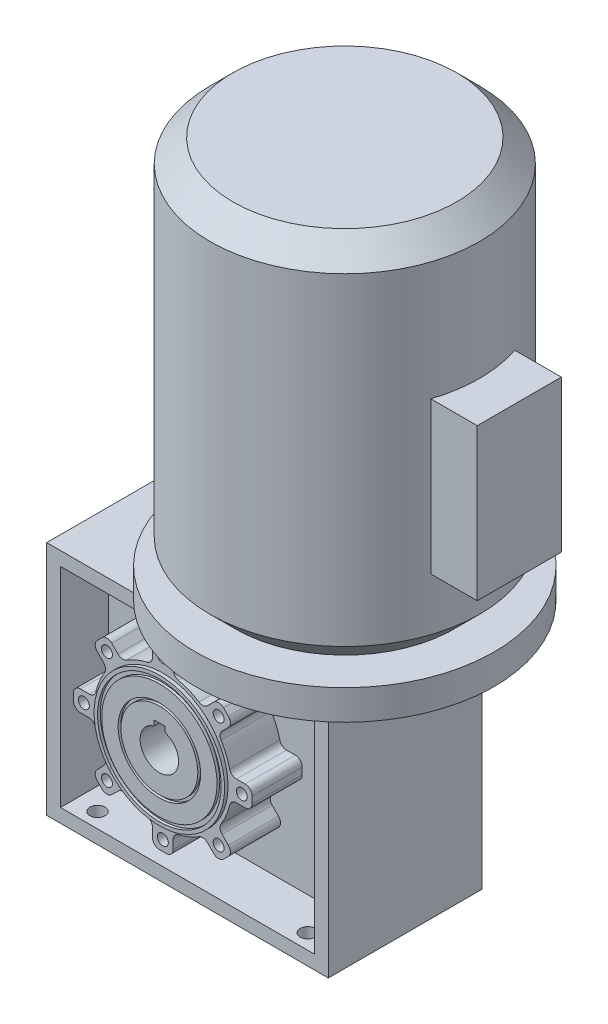
SolidWorks part; units mm, degrees
material "201 Annealed Stainless Steel (SS)"
ref_plane "Front Plane" through (0, 0, 0) normal (0, 0, 1) x (1, 0, 0)
ref_plane "Top Plane" through (0, 0, 0) normal (0, 1, 0) x (1, 0, 0)
ref_plane "Right Plane" through (0, 0, 0) normal (1, 0, 0) x (0, 0, -1)
sketch "Sketch1" plane through (0, 0, 0) normal (0, 0, 1) x (1, 0, 0)
  line L0 (214, -77.2819) -> (214, 49.2287) construction
  line L1 (61, -65.4596) -> (61, 55.7174) construction
  line L2 (125, 99.4164) -> (125, 103.3) construction
  line L3 (125, 103.3) -> (117, 103.3) construction
  line L4 (117, 103.3) -> (117, 99.4164) construction
  line L5 (121, 86) -> (121, 117.4858) construction
  line L8 (35, 0) -> (240, 0)
  line L9 (240, 0) -> (240, 172)
  line L10 (240, 172) -> (35, 172)
  line L11 (35, 172) -> (35, 0)
  circle A1 centre (121, 86) radius 14
  dimension "D1" = 86
  dimension "D2" = 86
  dimension "D6" = 28
  dimension "D3" = 205
  dimension "D4" = 172
  dimension "D5" = 35
  dimension "D7" = 93
  dimension "D8" = 60
  dimension "D9" = 31.3
  dimension "D10" = 8
extrude "Boss-Extrude1" add sketch "Sketch1" against normal blind 112
ref_plane "Plane1" through (0, 0, -56) normal (0, 0, 1) x (1, 0, 0)
sketch "Sketch3" plane through (0, 172, 0) normal (0, 1, 0) x (1, 0, 0)
  circle A1 centre (228, 65) radius 110
sketch "Sketch2" plane through (0, 0, -56) normal (0, 0, 1) x (1, 0, 0)
  line L0 (196, 62.1488) -> (196, 501.4136) construction
  line L1 (275.7058, 209.9069) -> (294.1112, 228.3123)
  line L2 (294.1112, 228.3123) -> (294.1112, 463.3395)
  line L3 (294.1112, 463.3395) -> (277.4507, 480)
  line L4 (277.4507, 480) -> (196, 480)
  line L5 (35, 0) -> (240, 0) construction
  line L6 (275.7058, 209.9069) -> (304.743, 209.9069)
  line L7 (304.743, 209.9069) -> (304.743, 199)
  line L8 (196, 209.9069) -> (275.7058, 209.9069) construction
  line L9 (196, 172) -> (196, 480)
  line L10 (304.743, 199) -> (237.6683, 199) construction
  line L11 (35, 0) -> (240, 0) construction
  line L12 (237.6683, 188.0931) -> (237.6683, 172)
  line L13 (240, 172) -> (35, 172) construction
  line L14 (237.6683, 172) -> (196, 172)
  line L15 (304.743, 199) -> (304.743, 188.0931)
  line L16 (304.743, 188.0931) -> (237.6683, 188.0931)
  dimension "D1" = 480
  dimension "D2" = 281
  dimension "D3" = 199
  dimension "D4" = 75
  dimension "D5" = 113
  dimension "D6" = 45
  dimension "D7" = 45
revolve "Motor" add sketch "Sketch2" angle 360 about L0
sketch "Sketch4" plane through (0, 0, 0) normal (0, 0, 1) x (1, 0, 0)
  line L8 (230, 10) -> (230, 162)
  line L9 (45, 10) -> (230, 10)
  line L10 (45, 162) -> (45, 10)
  line L11 (230, 162) -> (45, 162)
  line L12 (230, 10) -> (230, 162)
  line L13 (45, 10) -> (230, 10)
  line L14 (45, 162) -> (45, 10)
  line L15 (230, 162) -> (45, 162)
  circle A0 centre (121, 86) radius 50
  circle A1 centre (121, 86) radius 14 construction
  dimension "D2" = 100
  dimension "D1" = 10
extrude "Cut-Extrude1" cut sketch "Sketch4" against normal blind 35
sketch "Sketch5" plane through (0, 0, -112) normal (0, 0, -1) x (-1, 0, 0)
  line L4 (-230, 162) -> (-230, 10)
  line L5 (-45, 162) -> (-230, 162)
  line L6 (-45, 10) -> (-45, 162)
  line L7 (-230, 10) -> (-45, 10)
  line L8 (-230, 162) -> (-230, 10)
  line L9 (-45, 162) -> (-230, 162)
  line L10 (-45, 10) -> (-45, 162)
  line L11 (-230, 10) -> (-45, 10)
  circle A1 centre (-121, 86) radius 50
  circle A2 centre (-121, 86) radius 50
  dimension "D1" = 0
  dimension "D2" = 0
extrude "Cut-Extrude2" cut sketch "Sketch5" against normal blind 46
sketch "Sketch6" plane through (0, 0, 0) normal (0, 0, 1) x (1, 0, 0)
  line L0 (121, 86) -> (121, 219.6781) construction
  line L1 (121, 86) -> (299.9938, 86) construction
  line L2 (113.5, 135.4343) -> (113.5, 151)
  line L3 (113.5, 151) -> (128.5, 151)
  line L4 (128.5, 135.4343) -> (128.5, 151)
  circle A0 centre (121, 143.5) radius 4 construction
  circle A1 centre (121, 28.5) radius 4 construction
  arc A2 (128.5, 135.4343) -> (113.5, 135.4343) centre (121, 86) ccw
  circle A3 centre (121, 86) radius 50 construction
  circle A4 centre (121, 86) radius 57.5 construction
  point P14 (121, 151)
  dimension "D1" = 8
  dimension "D2" = 115
  dimension "D4" = 15
  dimension "D3" = 15
extrude "Boss-Extrude2" add sketch "Sketch6" against normal up to surface (112 mm away) up to face at (135, 86, -112)
ref_axis "Axis1" through (121, 86, -112) along (0, 0, 1)
sketch "Sketch7" plane through (0, 0, 0) normal (0, 0, 1) x (1, 0, 0)
  circle A0 centre (121, 143.5) radius 4 construction
  circle A1 centre (121, 143.5) radius 4
extrude "Cut-Extrude3" cut sketch "Sketch7" against normal through all
fillet "Fillet1" radius 5 8 edges at (128.5, 151, -17.5) (128.5, 135.4343, -17.5) (113.5, 135.4343, -17.5) (113.5, 151, -17.5) (128.5, 135.4343, -89) (128.5, 151, -89) (113.5, 151, -89) (113.5, 135.4343, -89)
pattern_circular "CirPattern1" count 8 over 360 about axis through (121, 86, -112) along (0, 0, 1) of "Boss-Extrude2", "Cut-Extrude3", "Fillet1"
sketch "Sketch8" plane through (0, 0, 0) normal (0, 0, 1) x (1, 0, 0)
  line L4 (88.4302, 129.1764) -> (83.8769, 133.7297)
  line L6 (88.4302, 129.1764) -> (83.8769, 133.7297)
  line L8 (76.8058, 133.7297) -> (73.2703, 130.1942)
  line L10 (76.8058, 133.7297) -> (73.2703, 130.1942)
  line L32 (73.2703, 123.1231) -> (77.8236, 118.5698)
  line L33 (73.2703, 123.1231) -> (77.8236, 118.5698)
  line L34 (67.4393, 93.5) -> (61, 93.5)
  line L35 (67.4393, 93.5) -> (61, 93.5)
  line L36 (56, 88.5) -> (56, 83.5)
  line L37 (56, 88.5) -> (56, 83.5)
  line L38 (61, 78.5) -> (67.4393, 78.5)
  line L39 (61, 78.5) -> (67.4393, 78.5)
  line L40 (77.8236, 53.4302) -> (73.2703, 48.8769)
  line L41 (77.8236, 53.4302) -> (73.2703, 48.8769)
  line L42 (73.2703, 41.8058) -> (76.8058, 38.2703)
  line L43 (73.2703, 41.8058) -> (76.8058, 38.2703)
  line L44 (83.8769, 38.2703) -> (88.4302, 42.8236)
  line L45 (83.8769, 38.2703) -> (88.4302, 42.8236)
  line L46 (113.5, 32.4393) -> (113.5, 26)
  line L47 (113.5, 32.4393) -> (113.5, 26)
  line L72 (118.5, 21) -> (123.5, 21)
  line L73 (118.5, 21) -> (123.5, 21)
  line L74 (128.5, 26) -> (128.5, 32.4393)
  line L75 (128.5, 26) -> (128.5, 32.4393)
  line L76 (153.5698, 42.8236) -> (158.1231, 38.2703)
  line L77 (153.5698, 42.8236) -> (158.1231, 38.2703)
  line L78 (165.1942, 38.2703) -> (168.7297, 41.8058)
  line L79 (165.1942, 38.2703) -> (168.7297, 41.8058)
  line L80 (168.7297, 48.8769) -> (164.1764, 53.4302)
  line L81 (168.7297, 48.8769) -> (164.1764, 53.4302)
  line L82 (174.5607, 78.5) -> (181, 78.5)
  line L83 (174.5607, 78.5) -> (181, 78.5)
  line L84 (186, 83.5) -> (186, 88.5)
  line L85 (186, 83.5) -> (186, 88.5)
  line L86 (181, 93.5) -> (174.5607, 93.5)
  line L87 (181, 93.5) -> (174.5607, 93.5)
  line L88 (164.1764, 118.5698) -> (168.7297, 123.1231)
  line L89 (164.1764, 118.5698) -> (168.7297, 123.1231)
  line L90 (168.7297, 130.1942) -> (165.1942, 133.7297)
  line L91 (168.7297, 130.1942) -> (165.1942, 133.7297)
  line L92 (158.1231, 133.7297) -> (153.5698, 129.1764)
  line L93 (158.1231, 133.7297) -> (153.5698, 129.1764)
  line L94 (128.5, 139.5607) -> (128.5, 146)
  line L95 (128.5, 139.5607) -> (128.5, 146)
  line L96 (123.5, 151) -> (118.5, 151)
  line L97 (123.5, 151) -> (118.5, 151)
  line L98 (113.5, 146) -> (113.5, 139.5607)
  line L99 (113.5, 146) -> (113.5, 139.5607)
  circle A0 centre (161.6586, 45.3414) radius 4 construction
  circle A1 centre (121, 28.5) radius 4 construction
  circle A2 centre (80.3414, 45.3414) radius 4 construction
  circle A3 centre (63.5, 86) radius 4 construction
  circle A4 centre (178.5, 86) radius 4 construction
  circle A5 centre (161.6586, 126.6586) radius 4 construction
  circle A6 centre (121, 86) radius 14 construction
  circle A7 centre (80.3414, 126.6586) radius 4 construction
  circle A24 centre (121, 143.5) radius 4 construction
  circle A25 centre (161.6586, 45.3414) radius 4
  circle A26 centre (121, 28.5) radius 4
  circle A27 centre (80.3414, 45.3414) radius 4
  circle A28 centre (63.5, 86) radius 4
  circle A29 centre (178.5, 86) radius 4
  circle A30 centre (161.6586, 126.6586) radius 4
  circle A31 centre (121, 86) radius 14
  circle A32 centre (80.3414, 126.6586) radius 4
  circle A33 centre (121, 143.5) radius 4
  arc A70 (168.7297, 123.1231) -> (168.7297, 130.1942) centre (165.1942, 126.6586) ccw
  arc A71 (168.7297, 123.1231) -> (168.7297, 130.1942) centre (165.1942, 126.6586) ccw
  arc A72 (165.1942, 133.7297) -> (158.1231, 133.7297) centre (161.6586, 130.1942) ccw
  arc A73 (165.1942, 133.7297) -> (158.1231, 133.7297) centre (161.6586, 130.1942) ccw
  arc A74 (147.3948, 128.4654) -> (153.5698, 129.1764) centre (150.0343, 132.712) ccw
  arc A76 (147.3948, 128.4654) -> (153.5698, 129.1764) centre (150.0343, 132.712) ccw
  arc A78 (147.3948, 128.4654) -> (132.3636, 134.6916) centre (121, 86) ccw
  arc A80 (147.3948, 128.4654) -> (132.3636, 134.6916) centre (121, 86) ccw
  arc A82 (128.5, 139.5607) -> (132.3636, 134.6916) centre (133.5, 139.5607) ccw
  arc A84 (128.5, 139.5607) -> (132.3636, 134.6916) centre (133.5, 139.5607) ccw
  arc A86 (128.5, 146) -> (123.5, 151) centre (123.5, 146) ccw
  arc A88 (128.5, 146) -> (123.5, 151) centre (123.5, 146) ccw
  arc A90 (118.5, 151) -> (113.5, 146) centre (118.5, 146) ccw
  arc A92 (118.5, 151) -> (113.5, 146) centre (118.5, 146) ccw
  arc A94 (109.6364, 134.6916) -> (113.5, 139.5607) centre (108.5, 139.5607) ccw
  arc A96 (109.6364, 134.6916) -> (113.5, 139.5607) centre (108.5, 139.5607) ccw
  arc A98 (109.6364, 134.6916) -> (94.6052, 128.4654) centre (121, 86) ccw
  arc A100 (109.6364, 134.6916) -> (94.6052, 128.4654) centre (121, 86) ccw
  arc A102 (88.4302, 129.1764) -> (94.6052, 128.4654) centre (91.9657, 132.712) ccw
  arc A104 (88.4302, 129.1764) -> (94.6052, 128.4654) centre (91.9657, 132.712) ccw
  arc A106 (83.8769, 133.7297) -> (76.8058, 133.7297) centre (80.3414, 130.1942) ccw
  arc A108 (83.8769, 133.7297) -> (76.8058, 133.7297) centre (80.3414, 130.1942) ccw
  arc A110 (73.2703, 130.1942) -> (73.2703, 123.1231) centre (76.8058, 126.6586) ccw
  arc A112 (73.2703, 130.1942) -> (73.2703, 123.1231) centre (76.8058, 126.6586) ccw
  arc A114 (78.5346, 112.3948) -> (77.8236, 118.5698) centre (74.288, 115.0343) ccw
  arc A116 (78.5346, 112.3948) -> (77.8236, 118.5698) centre (74.288, 115.0343) ccw
  arc A118 (78.5346, 112.3948) -> (72.3084, 97.3636) centre (121, 86) ccw
  arc A120 (78.5346, 112.3948) -> (72.3084, 97.3636) centre (121, 86) ccw
  arc A122 (67.4393, 93.5) -> (72.3084, 97.3636) centre (67.4393, 98.5) ccw
  arc A124 (67.4393, 93.5) -> (72.3084, 97.3636) centre (67.4393, 98.5) ccw
  arc A126 (61, 93.5) -> (56, 88.5) centre (61, 88.5) ccw
  arc A128 (61, 93.5) -> (56, 88.5) centre (61, 88.5) ccw
  arc A130 (56, 83.5) -> (61, 78.5) centre (61, 83.5) ccw
  arc A132 (56, 83.5) -> (61, 78.5) centre (61, 83.5) ccw
  arc A134 (72.3084, 74.6364) -> (67.4393, 78.5) centre (67.4393, 73.5) ccw
  arc A136 (72.3084, 74.6364) -> (67.4393, 78.5) centre (67.4393, 73.5) ccw
  arc A138 (72.3084, 74.6364) -> (78.5346, 59.6052) centre (121, 86) ccw
  arc A140 (72.3084, 74.6364) -> (78.5346, 59.6052) centre (121, 86) ccw
  arc A142 (77.8236, 53.4302) -> (78.5346, 59.6052) centre (74.288, 56.9657) ccw
  arc A144 (77.8236, 53.4302) -> (78.5346, 59.6052) centre (74.288, 56.9657) ccw
  arc A146 (73.2703, 48.8769) -> (73.2703, 41.8058) centre (76.8058, 45.3414) ccw
  arc A147 (73.2703, 48.8769) -> (73.2703, 41.8058) centre (76.8058, 45.3414) ccw
  arc A148 (76.8058, 38.2703) -> (83.8769, 38.2703) centre (80.3414, 41.8058) ccw
  arc A149 (76.8058, 38.2703) -> (83.8769, 38.2703) centre (80.3414, 41.8058) ccw
  arc A150 (94.6052, 43.5346) -> (88.4302, 42.8236) centre (91.9657, 39.288) ccw
  arc A151 (94.6052, 43.5346) -> (88.4302, 42.8236) centre (91.9657, 39.288) ccw
  arc A152 (94.6052, 43.5346) -> (109.6364, 37.3084) centre (121, 86) ccw
  arc A153 (94.6052, 43.5346) -> (109.6364, 37.3084) centre (121, 86) ccw
  arc A154 (113.5, 32.4393) -> (109.6364, 37.3084) centre (108.5, 32.4393) ccw
  arc A155 (113.5, 32.4393) -> (109.6364, 37.3084) centre (108.5, 32.4393) ccw
  arc A156 (113.5, 26) -> (118.5, 21) centre (118.5, 26) ccw
  arc A157 (113.5, 26) -> (118.5, 21) centre (118.5, 26) ccw
  arc A158 (123.5, 21) -> (128.5, 26) centre (123.5, 26) ccw
  arc A159 (123.5, 21) -> (128.5, 26) centre (123.5, 26) ccw
  arc A160 (132.3636, 37.3084) -> (128.5, 32.4393) centre (133.5, 32.4393) ccw
  arc A161 (132.3636, 37.3084) -> (128.5, 32.4393) centre (133.5, 32.4393) ccw
  arc A162 (132.3636, 37.3084) -> (147.3948, 43.5346) centre (121, 86) ccw
  arc A163 (132.3636, 37.3084) -> (147.3948, 43.5346) centre (121, 86) ccw
  arc A164 (153.5698, 42.8236) -> (147.3948, 43.5346) centre (150.0343, 39.288) ccw
  arc A165 (153.5698, 42.8236) -> (147.3948, 43.5346) centre (150.0343, 39.288) ccw
  arc A166 (158.1231, 38.2703) -> (165.1942, 38.2703) centre (161.6586, 41.8058) ccw
  arc A167 (158.1231, 38.2703) -> (165.1942, 38.2703) centre (161.6586, 41.8058) ccw
  arc A168 (168.7297, 41.8058) -> (168.7297, 48.8769) centre (165.1942, 45.3414) ccw
  arc A169 (168.7297, 41.8058) -> (168.7297, 48.8769) centre (165.1942, 45.3414) ccw
  arc A170 (163.4654, 59.6052) -> (164.1764, 53.4302) centre (167.712, 56.9657) ccw
  arc A171 (163.4654, 59.6052) -> (164.1764, 53.4302) centre (167.712, 56.9657) ccw
  arc A172 (163.4654, 59.6052) -> (169.6916, 74.6364) centre (121, 86) ccw
  arc A173 (163.4654, 59.6052) -> (169.6916, 74.6364) centre (121, 86) ccw
  arc A174 (174.5607, 78.5) -> (169.6916, 74.6364) centre (174.5607, 73.5) ccw
  arc A175 (174.5607, 78.5) -> (169.6916, 74.6364) centre (174.5607, 73.5) ccw
  arc A176 (181, 78.5) -> (186, 83.5) centre (181, 83.5) ccw
  arc A177 (181, 78.5) -> (186, 83.5) centre (181, 83.5) ccw
  arc A178 (186, 88.5) -> (181, 93.5) centre (181, 88.5) ccw
  arc A179 (186, 88.5) -> (181, 93.5) centre (181, 88.5) ccw
  arc A180 (169.6916, 97.3636) -> (174.5607, 93.5) centre (174.5607, 98.5) ccw
  arc A181 (169.6916, 97.3636) -> (174.5607, 93.5) centre (174.5607, 98.5) ccw
  arc A182 (169.6916, 97.3636) -> (163.4654, 112.3948) centre (121, 86) ccw
  arc A183 (169.6916, 97.3636) -> (163.4654, 112.3948) centre (121, 86) ccw
  arc A184 (164.1764, 118.5698) -> (163.4654, 112.3948) centre (167.712, 115.0343) ccw
  arc A185 (164.1764, 118.5698) -> (163.4654, 112.3948) centre (167.712, 115.0343) ccw
  dimension "D1" = 0
extrude "Boss-Extrude one side" add sketch "Sketch8" along normal blind 1.5
sketch "Sketch9" plane through (0, 0, 1.5) normal (0, 0, 1) x (1, 0, 0)
  circle A0 centre (121, 86) radius 47.5
  circle A2 centre (121, 86) radius 14
  circle A3 centre (121, 86) radius 14 construction
  dimension "D1" = 95
extrude "Boss-Extrude5" add sketch "Sketch9" along normal blind 2.5
sketch "Sketch10" plane through (0, 0, 4) normal (0, 0, 1) x (1, 0, 0)
  circle A0 centre (121, 86) radius 45
  circle A1 centre (121, 86) radius 42
  dimension "D1" = 90
  dimension "D2" = 84
extrude "Cut-Extrude4" cut sketch "Sketch10" against normal blind 2
sketch "Sketch11" plane through (0, 0, 4) normal (0, 0, 1) x (1, 0, 0)
  circle A0 centre (121, 86) radius 30
  circle A1 centre (121, 86) radius 14 construction
  circle A2 centre (121, 86) radius 28
  dimension "D1" = 60
  dimension "D2" = 2
extrude "Cut-Extrude5" cut sketch "Sketch11" against normal up to surface (2 mm away) up to face at (163, 86, 2)
sketch "Sketch12" plane through (240, 0, 0) normal (1, 0, 0) x (0, 0, -1)
  line L0 (56, 158.4) -> (56, -158.4) construction
  line L1 (25.4071, 377.0348) -> (86.5929, 377.0348)
  line L2 (25.4071, 377.0348) -> (25.4071, 266.6375)
  line L3 (25.4071, 266.6375) -> (86.5929, 266.6375)
  line L4 (86.5929, 377.0348) -> (86.5929, 266.6375)
  line L5 (25.4071, 377.0348) -> (86.5929, 266.6375) construction
  line L6 (25.4071, 266.6375) -> (86.5929, 377.0348) construction
  point P0 (56, 321.8362)
extrude "Boss-Extrude6" add sketch "Sketch12" along normal offset from surface (83 mm away) 288 up to face at (35, 86, -56)
mirror "Mirror1" about plane through (0, 0, -56) normal (0, 0, 1) of "Cut-Extrude5", "Cut-Extrude4", "Boss-Extrude5", "Boss-Extrude one side"
sketch "Sketch14" plane through (0, 0, 0) normal (0, -1, 0) x (1, 0, 0)
  line L0 (240, -56) -> (306.3943, -56) construction
  line L1 (240, -112) -> (240, 0) construction
  line L2 (137.5, -60.53) -> (137.5, 72.4647) construction
  circle A0 centre (214, -11) radius 5.5
  circle A1 centre (214, -101) radius 5.5
  circle A2 centre (61, -101) radius 5.5
  circle A3 centre (61, -11) radius 5.5
  dimension "D1" = 90
  dimension "D2" = 11
  dimension "D3" = 153
extrude "Cut-Extrude6" cut sketch "Sketch14" against normal blind 15
sketch "Sketch15" plane through (0, 0, 4) normal (0, 0, 1) x (1, 0, 0)
  line L0 (125, 99.4164) -> (125, 103.3) construction
  line L1 (125, 103.3) -> (117, 103.3) construction
  line L2 (117, 103.3) -> (117, 99.4164) construction
  line L3 (125, 99.4164) -> (125, 103.3)
  line L4 (125, 103.3) -> (117, 103.3)
  line L5 (117, 103.3) -> (117, 99.4164)
  circle A0 centre (121, 86) radius 14 construction
  arc A1 (125, 99.4164) -> (117, 99.4164) centre (121, 86) ccw
extrude "Cut-Extrude7" cut sketch "Sketch15" against normal through all
